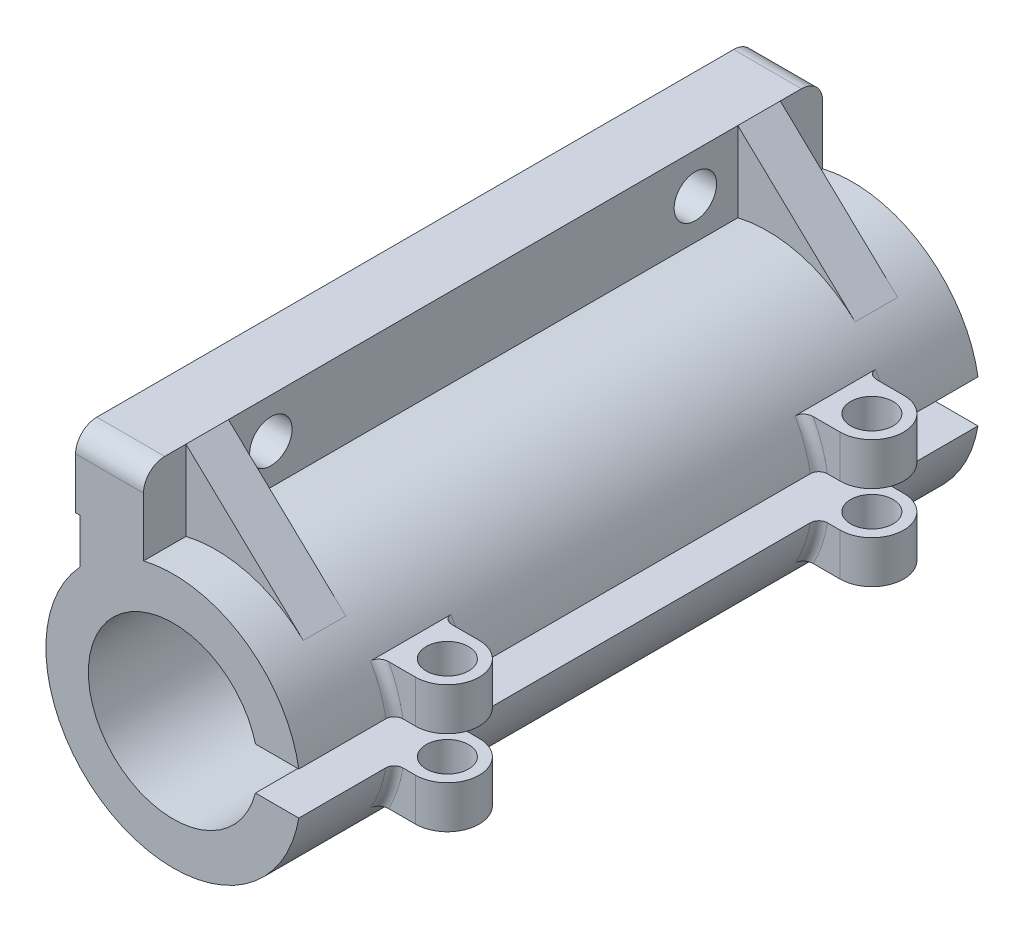
SolidWorks part; units mm, degrees
ref_plane "Front Plane" through (0, 0, 0) normal (0, 0, 1) x (1, 0, 0)
ref_plane "Top Plane" through (0, 0, 0) normal (0, 1, 0) x (1, 0, 0)
ref_plane "Right Plane" through (0, 0, 0) normal (1, 0, 0) x (0, 0, -1)
sketch "Sketch1" plane through (0, 0, 0) normal (0, 0, 1) x (1, 0, 0)
  line L0 (-3.5, 24) -> (10.3252, 10.8808)
  line L1 (-11, 24) -> (-11.5, 24)
  line L2 (-11.5, 24) -> (-11.5, 15.5)
  line L3 (-11, 15.5) -> (-11.5, 15.5)
  line L5 (-11, 10.198) -> (-11, 15.5)
  line L6 (-11, 24) -> (-3.5, 24)
  line L7 (-3.5, 24) -> (-3.5, 14.586)
  line L12 (9.6825, 2.5) -> (14.7902, 2.5)
  line L14 (14.7902, -2.5) -> (9.6825, -2.5)
  arc A0 (9.6825, 2.5) -> (9.6825, -2.5) centre (0, 0) ccw
  arc A1 (-11, 10.198) -> (14.7902, -2.5) centre (0, 0) ccw
  arc A2 (14.7902, 2.5) -> (-3.5, 14.586) centre (0, 0) ccw
extrude "Boss-Extrude1" add sketch "Sketch1" along normal mid plane 80 contours A1 L7 L6 L1 L2 L3 L5 A0 region at (-3.9908, 19.293, 0)
extrude "Boss-Extrude2" add sketch "Sketch1<3>" along normal blind 5 from offset 30 contours A1 L0 L7 region at (0.1868, 17.6161, 0)
sketch "Sketch1<3>" plane through (0, 0, 0) normal (0, 0, 1) x (1, 0, 0) same geometry as "Sketch1"
extrude "Boss-Extrude3" add sketch "Sketch1<4>" against normal blind 5 from offset 30 contours A1 L0 L7 region at (0.1868, 17.6161, 0) offset against normal yes
sketch "Sketch1<4>" plane through (0, 0, 0) normal (0, 0, 1) x (1, 0, 0) same geometry as "Sketch1"
sketch "Sketch2" plane through (0, 0, 0) normal (1, 0, 0) x (0, 0, -1)
  line L0 (30, 24) -> (30, 14.586) construction
  circle A0 centre (-25, 19.293) radius 2.5
  circle A1 centre (25, 19.293) radius 2.5
  point P4 (30, 19.293)
extrude "Cut-Extrude1" cut sketch "Sketch2" against normal blind 15
sketch "Sketch4" plane through (0, 0, 0) normal (0, 1, 0) x (1, 0, 0)
  line L0 (17.2902, 21.25) -> (12.2902, 21.25)
  line L3 (12.2902, 21.25) -> (12.2902, 28.75)
  line L4 (12.2902, 28.75) -> (17.2902, 28.75)
  line L7 (12.2902, -28.75) -> (17.2902, -28.75)
  line L8 (12.2902, -21.25) -> (12.2902, -28.75)
  line L9 (17.2902, -21.25) -> (12.2902, -21.25)
  arc A0 (17.2902, 21.25) -> (17.2902, 28.75) centre (17.2902, 25) ccw
  circle A1 centre (17.2902, 25) radius 2.5
  circle A2 centre (17.2902, -25) radius 2.5
  arc A3 (17.2902, -21.25) -> (17.2902, -28.75) centre (17.2902, -25) cw
extrude "Boss-Extrude4" add sketch "Sketch4" along normal blind 5 from offset 2.5
extrude "Boss-Extrude5" add sketch "Sketch4<2>" against normal blind 5 from offset 2.5 offset against normal yes
sketch "Sketch4<2>" plane through (0, 0, 0) normal (0, 1, 0) x (1, 0, 0) same geometry as "Sketch4"
fillet "Fillet1" radius 1 8 edges at (14.1135, 5.0803, 21.25) (14.1135, 5.0803, 28.75) (14.1135, -5.0803, -28.75) (14.1135, 5.0803, -28.75) (14.1135, -5.0803, 21.25) (14.1135, -5.0803, 28.75) (14.1135, -5.0803, -21.25) (14.1135, 5.0803, -21.25)
fillet "Fillet2" radius 2.5 2 edges at (-7.5, 24, -40) (-7.5, 24, 40)
